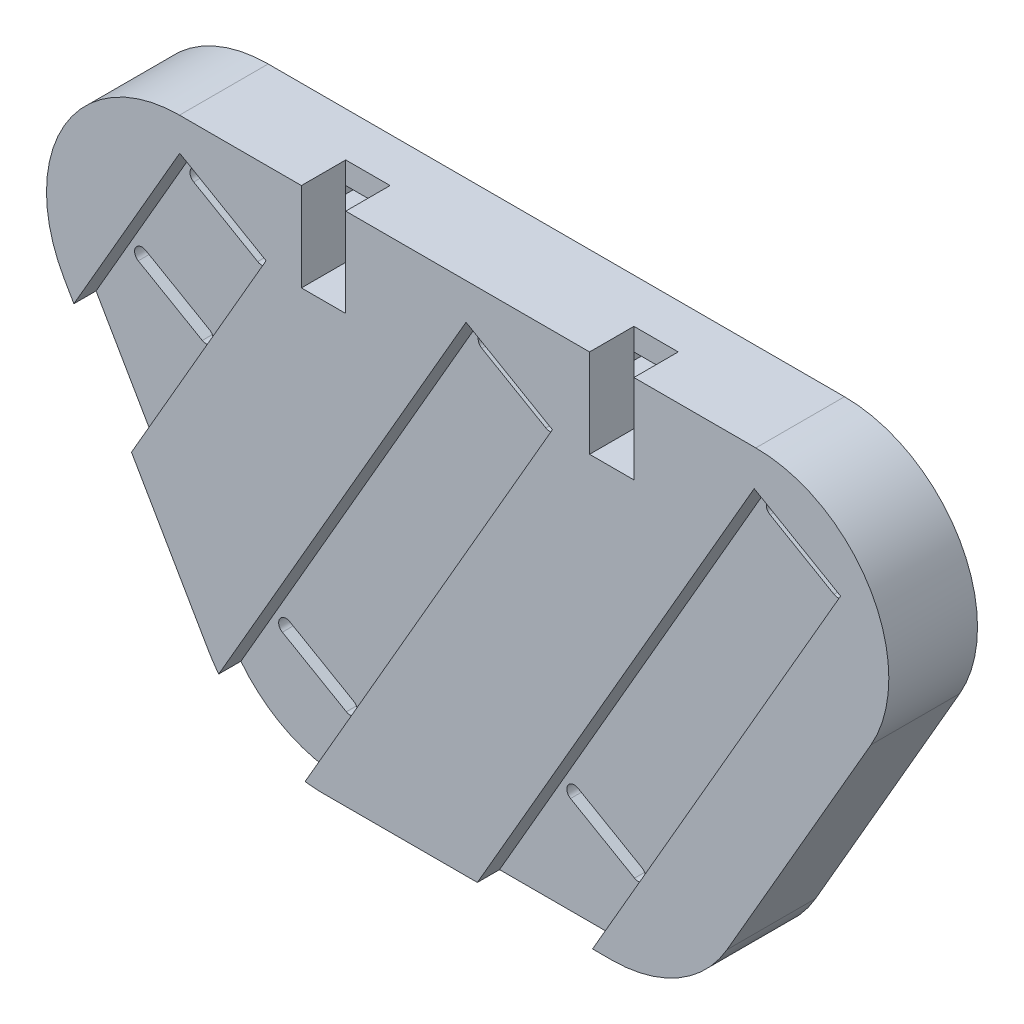
SolidWorks part; units mm, degrees
ref_plane "Front Plane" through (0, 0, 0) normal (0, 0, 1) x (1, 0, 0)
ref_plane "Top Plane" through (0, 0, 0) normal (0, 1, 0) x (1, 0, 0)
ref_plane "Right Plane" through (0, 0, 0) normal (1, 0, 0) x (0, 0, -1)
sketch "Sketch1" plane through (0, 0, 0) normal (0, 0, 1) x (1, 0, 0)
  line L0 (0, 0) -> (-19.5, 0) construction
  line L1 (-9.75, -16.8875) -> (-29.25, -16.8875) construction
  line L2 (0, 0) -> (-9.75, -16.8875) construction
  line L3 (-9.75, -16.8875) -> (-19.5, 0) construction
  line L4 (-19.5, 0) -> (-29.25, -16.8875) construction
  line L5 (-29.25, -16.8875) -> (-39, 0) construction
  line L6 (-39, 0) -> (-19.5, 0) construction
  line L7 (8.9827, 0.5584) -> (-5.4199, -24.3875) construction
  line L8 (-5.4199, -24.3875) -> (-33.5801, -24.3875) construction
  line L9 (-33.5801, -24.3875) -> (-47.9827, 0.5584) construction
  line L10 (-43.9749, 7.5) -> (4.9749, 7.5) construction
  line L11 (7.7942, -4.5) -> (-1.9558, -21.3875)
  line L12 (-9.75, -25.8875) -> (-29.25, -25.8875)
  line L13 (-37.0442, -21.3875) -> (-46.7942, -4.5)
  line L14 (-39, 9) -> (0, 9)
  line L15 (1.7814, -11.9145) -> (3.0804, -12.6645) construction
  line L16 (-19.5, -24.3875) -> (-19.5, -25.8875) construction
  line L17 (-40.7814, -11.9145) -> (-42.0804, -12.6645) construction
  line L18 (-19.5, 7.5) -> (-19.5, 9) construction
  circle A0 centre (-29.25, -16.8875) radius 7.5
  circle A1 centre (-19.5, 0) radius 7.5
  circle A2 centre (0, 0) radius 7.5
  circle A3 centre (0, 0) radius 7.5
  circle A4 centre (-9.75, -16.8875) radius 7.5
  circle A5 centre (-39, 0) radius 7.5
  arc A6 (7.7942, -4.5) -> (0, 9) centre (0, 0) ccw
  arc A7 (-39, 9) -> (-46.7942, -4.5) centre (-39, 0) ccw
  arc A8 (-1.9558, -21.3875) -> (-9.75, -25.8875) centre (-9.75, -16.8875) cw
  arc A9 (-29.25, -25.8875) -> (-37.0442, -21.3875) centre (-29.25, -16.8875) cw
  point P28 (1.7814, -11.9145)
  point P30 (-19.5, -24.3875)
  point P32 (-40.7814, -11.9145)
  point P35 (-19.5, 9)
  dimension "D2" = 15
  dimension "D3" = 19.5
  dimension "D4" = 1.5
  dimension "D5" = 1.5
  dimension "D1" = 0.25
extrude "Boss-Extrude1" add sketch "Sketch1" along normal blind 3
sketch "Sketch2" plane through (0, 0, 3) normal (0, 0, 1) x (1, 0, 0)
  line L0 (-1.9558, -21.3875) -> (7.7942, -4.5) construction
  line L1 (0, 9) -> (-39, 9) construction
  line L2 (-46.7942, -4.5) -> (-37.0442, -21.3875) construction
  line L3 (-29.25, -25.8875) -> (-9.75, -25.8875) construction
  line L4 (-1.9558, -21.3875) -> (7.7942, -4.5)
  line L5 (0, 9) -> (-39, 9)
  line L6 (-46.7942, -4.5) -> (-37.0442, -21.3875)
  line L7 (-29.25, -25.8875) -> (-9.75, -25.8875)
  line L8 (4.0401, 1.9976) -> (-0.2901, 4.4976) construction
  line L9 (3.7901, 1.5646) -> (-0.5401, 4.0646)
  line L10 (4.2901, 2.4306) -> (-0.0401, 4.9306)
  line L11 (-9.4599, -21.3851) -> (-13.7901, -18.8851) construction
  line L12 (-9.7099, -21.8181) -> (-14.0401, -19.3181)
  line L13 (-9.2099, -20.9521) -> (-13.5401, -18.4521)
  line L14 (1.875, 3.2476) -> (-11.625, -20.1351) construction
  line L15 (-31.125, -20.1351) -> (-29.25, -16.8875) construction
  line L16 (0, 0) -> (1.875, 3.2476) construction
  line L17 (1.875, 3.2476) -> (3.75, 6.4952) construction
  line L18 (-11.625, -20.1351) -> (-13.5, -23.3827) construction
  line L19 (-11.625, -20.1351) -> (-9.75, -16.8875) construction
  line L20 (-17.625, 3.2476) -> (-15.75, 6.4952) construction
  line L21 (-17.625, 3.2476) -> (-31.125, -20.1351) construction
  line L22 (-19.5, 0) -> (-17.625, 3.2476) construction
  line L23 (-31.125, -20.1351) -> (-33, -23.3827) construction
  line L24 (-15.4599, 1.9976) -> (-19.7901, 4.4976) construction
  line L25 (-15.7099, 1.5646) -> (-20.0401, 4.0646)
  line L26 (-15.2099, 2.4306) -> (-19.5401, 4.9306)
  line L27 (-28.9599, -21.3851) -> (-33.2901, -18.8851) construction
  line L28 (-29.2099, -21.8181) -> (-33.5401, -19.3181)
  line L29 (-28.7099, -20.9521) -> (-33.0401, -18.4521)
  line L30 (-34.9599, 1.9976) -> (-39.2901, 4.4976) construction
  line L31 (-35.2099, 1.5646) -> (-39.5401, 4.0646)
  line L32 (-34.7099, 2.4306) -> (-39.0401, 4.9306)
  line L33 (-38.7099, -4.4976) -> (-43.0401, -1.9976) construction
  line L34 (-38.9599, -4.9306) -> (-43.2901, -2.4306)
  line L35 (-38.4599, -4.0646) -> (-42.7901, -1.5646)
  line L36 (-37.125, 3.2476) -> (-40.875, -3.2476) construction
  line L37 (-37.125, 3.2476) -> (-35.25, 6.4952) construction
  line L38 (-40.875, -3.2476) -> (-42.75, -6.4952) construction
  line L39 (-37.125, 3.2476) -> (-39, 0) construction
  arc A0 (-9.75, -25.8875) -> (-1.9558, -21.3875) centre (-9.75, -16.8875) ccw construction
  arc A1 (7.7942, -4.5) -> (0, 9) centre (0, 0) ccw construction
  arc A2 (-39, 9) -> (-46.7942, -4.5) centre (-39, 0) ccw construction
  arc A3 (-37.0442, -21.3875) -> (-29.25, -25.8875) centre (-29.25, -16.8875) ccw construction
  arc A4 (-9.75, -25.8875) -> (-1.9558, -21.3875) centre (-9.75, -16.8875) ccw
  arc A5 (7.7942, -4.5) -> (0, 9) centre (0, 0) ccw
  arc A6 (-39, 9) -> (-46.7942, -4.5) centre (-39, 0) ccw
  arc A7 (-37.0442, -21.3875) -> (-29.25, -25.8875) centre (-29.25, -16.8875) ccw
  circle A8 centre (-39, 0) radius 7.5 construction
  circle A9 centre (-29.25, -16.8875) radius 7.5 construction
  circle A10 centre (-19.5, 0) radius 7.5 construction
  circle A11 centre (-9.75, -16.8875) radius 7.5 construction
  circle A12 centre (0, 0) radius 7.5 construction
  circle A13 centre (-39, 0) radius 7.5
  circle A14 centre (-29.25, -16.8875) radius 7.5
  circle A15 centre (-19.5, 0) radius 7.5
  circle A16 centre (-9.75, -16.8875) radius 7.5
  circle A17 centre (0, 0) radius 7.5
  arc A18 (3.7901, 1.5646) -> (4.2901, 2.4306) centre (4.0401, 1.9976) ccw
  arc A19 (-0.0401, 4.9306) -> (-0.5401, 4.0646) centre (-0.2901, 4.4976) ccw
  arc A20 (-9.7099, -21.8181) -> (-9.2099, -20.9521) centre (-9.4599, -21.3851) ccw
  arc A21 (-13.5401, -18.4521) -> (-14.0401, -19.3181) centre (-13.7901, -18.8851) ccw
  arc A22 (-15.7099, 1.5646) -> (-15.2099, 2.4306) centre (-15.4599, 1.9976) ccw
  arc A23 (-19.5401, 4.9306) -> (-20.0401, 4.0646) centre (-19.7901, 4.4976) ccw
  arc A24 (-29.2099, -21.8181) -> (-28.7099, -20.9521) centre (-28.9599, -21.3851) ccw
  arc A25 (-33.0401, -18.4521) -> (-33.5401, -19.3181) centre (-33.2901, -18.8851) ccw
  arc A26 (-35.2099, 1.5646) -> (-34.7099, 2.4306) centre (-34.9599, 1.9976) ccw
  arc A27 (-39.0401, 4.9306) -> (-39.5401, 4.0646) centre (-39.2901, 4.4976) ccw
  arc A28 (-38.9599, -4.9306) -> (-38.4599, -4.0646) centre (-38.7099, -4.4976) ccw
  arc A29 (-42.7901, -1.5646) -> (-43.2901, -2.4306) centre (-43.0401, -1.9976) ccw
  point P8 (-37.125, 3.2476)
  point P25 (1.875, 3.2476)
  point P32 (-11.625, -20.1351)
  point P45 (-17.625, 3.2476)
  point P52 (-31.125, -20.1351)
  point P64 (-40.875, -3.2476)
  circle M1 centre (-9.75, -16.8875) radius 7.5
  circle M2 centre (0, 0) radius 7.5
  arc M3 (7.7942, -4.5) -> (0, 9) centre (0, 0) ccw
  line M4 (0, 9) -> (-39, 9)
  arc M5 (-39, 9) -> (-46.7942, -4.5) centre (-39, 0) ccw
  line M6 (-46.7942, -4.5) -> (-37.0442, -21.3875)
  arc M7 (-37.0442, -21.3875) -> (-29.25, -25.8875) centre (-29.25, -16.8875) ccw
  line M8 (-29.25, -25.8875) -> (-9.75, -25.8875)
  arc M9 (-9.75, -25.8875) -> (-1.9558, -21.3875) centre (-9.75, -16.8875) ccw
  line M10 (-1.9558, -21.3875) -> (7.7942, -4.5)
  circle M11 centre (-19.5, 0) radius 7.5
  circle M12 centre (-29.25, -16.8875) radius 7.5
  circle M13 centre (-39, 0) radius 7.5
  dimension "D1" = 1
  dimension "D2" = 5
extrude "Boss-Extrude2" add sketch "Sketch2" along normal blind 1.5 contours A21 L13 A20 L12 M1 | M10 M3 M4 M5 M6 M7 M8 M9 M2 M11 M13 M12 M1 | A19 L10 A18 L9 M2 | A23 L26 A22 L25 M11 | A25 L29 A24 L28 M12 | A29 L35 A28 L34 A27 L32 A26 L31 M13 region at (-5.5841, -24.103, 3) region at (-39, 0, 3) region at (-29.1865, -16.7776, 3) region at (-19.5635, -0.1099, 3) region at (-9.6865, -16.7776, 3) region at (-0.0635, -0.1099, 3)
sketch "Sketch3" plane through (0, 0, 4.5) normal (0, 0, 1) x (1, 0, 0)
  line L0 (-46.7942, -4.5) -> (-37.0442, -21.3875) construction
  line L1 (-29.25, -25.8875) -> (-9.75, -25.8875) construction
  line L2 (-1.9558, -21.3875) -> (7.7942, -4.5) construction
  line L3 (0, 9) -> (-39, 9) construction
  line L4 (-46.7942, -4.5) -> (-37.0442, -21.3875)
  line L5 (-29.25, -25.8875) -> (-9.75, -25.8875)
  line L6 (-1.9558, -21.3875) -> (7.7942, -4.5)
  line L7 (0, 9) -> (-39, 9)
  line L8 (5.7353, 3.1839) -> (-9.6397, -23.4464)
  line L9 (5.7353, 3.1839) -> (-0.1103, 6.5589)
  line L10 (-9.6397, -23.4464) -> (-15.4853, -20.0714)
  line L11 (-0.1103, 6.5589) -> (-15.4853, -20.0714)
  line L12 (5.7353, 3.1839) -> (-15.4853, -20.0714) construction
  line L13 (-9.6397, -23.4464) -> (-0.1103, 6.5589) construction
  line L14 (-11.625, -20.1351) -> (-13.5, -23.3827) construction
  line L15 (-11.625, -20.1351) -> (-13.5, -23.3827) construction
  line L16 (-11.875, -20.5681) -> (-12.5625, -21.7589) construction
  line L17 (-9.7099, -21.8181) -> (-14.0401, -19.3181) construction
  line L18 (-14.2231, -18.6351) -> (-14.5478, -18.4476) construction
  line L19 (1.875, 3.2476) -> (-11.625, -20.1351) construction
  line L20 (1.875, 3.2476) -> (-11.625, -20.1351) construction
  line L21 (-31.125, -20.1351) -> (-33, -23.3827) construction
  line L22 (-17.625, 3.2476) -> (-31.125, -20.1351) construction
  line L23 (-31.125, -20.1351) -> (-33, -23.3827) construction
  line L24 (-17.625, 3.2476) -> (-31.125, -20.1351) construction
  line L25 (-13.7647, 3.1839) -> (-29.1397, -23.4464)
  line L26 (-13.7647, 3.1839) -> (-19.6103, 6.5589)
  line L27 (-29.1397, -23.4464) -> (-34.9853, -20.0714)
  line L28 (-19.6103, 6.5589) -> (-34.9853, -20.0714)
  line L29 (-13.7647, 3.1839) -> (-34.9853, -20.0714) construction
  line L30 (-29.1397, -23.4464) -> (-19.6103, 6.5589) construction
  line L31 (-32.8571, -19.1351) -> (-34.0478, -18.4476) construction
  line L32 (-31.375, -20.5681) -> (-32.0625, -21.7589) construction
  line L33 (-29.2099, -21.8181) -> (-33.5401, -19.3181) construction
  line L34 (-33.1397, 3.4004) -> (-42.2476, -12.375)
  line L35 (-33.1397, 3.4004) -> (-38.9853, 6.7754)
  line L36 (-9.6397, -23.4464) -> (-15.4853, -20.0714)
  line L37 (-38.9853, 6.7754) -> (-46.1447, -5.625)
  line L38 (-33.1397, 3.4004) -> (-45.4579, -6.8146) construction
  line L39 (-42.2476, -12.375) -> (-38.9853, 6.7754) construction
  line L40 (-37.125, 3.2476) -> (-40.875, -3.2476) construction
  line L41 (-36.875, 3.6806) -> (-36.0625, 5.0879) construction
  line L42 (-34.7099, 2.4306) -> (-39.0401, 4.9306) construction
  line L43 (-36.0625, 5.0879) -> (-35.25, 6.4952) construction
  line L44 (-9.6397, -23.4464) -> (-11.049, -25.8875)
  line L45 (-15.4853, -20.0714) -> (-18.8433, -25.8875)
  line L47 (-29.1397, -23.4464) -> (-34.9853, -20.0714)
  line L48 (-29.1397, -23.4464) -> (-30.4988, -25.8004)
  line L49 (-34.9853, -20.0714) -> (-36.3444, -22.4254)
  arc A0 (-37.0442, -21.3875) -> (-29.25, -25.8875) centre (-29.25, -16.8875) ccw construction
  arc A1 (-9.75, -25.8875) -> (-1.9558, -21.3875) centre (-9.75, -16.8875) ccw construction
  arc A2 (7.7942, -4.5) -> (0, 9) centre (0, 0) ccw construction
  arc A3 (-39, 9) -> (-46.7942, -4.5) centre (-39, 0) ccw construction
  arc A4 (-37.0442, -21.3875) -> (-29.25, -25.8875) centre (-29.25, -16.8875) ccw
  arc A5 (-9.75, -25.8875) -> (-1.9558, -21.3875) centre (-9.75, -16.8875) ccw
  arc A6 (7.7942, -4.5) -> (0, 9) centre (0, 0) ccw
  arc A7 (-39, 9) -> (-46.7942, -4.5) centre (-39, 0) ccw
  arc A8 (-13.5401, -18.4521) -> (-14.0401, -19.3181) centre (-13.7901, -18.8851) ccw construction
  arc A9 (-33.0401, -18.4521) -> (-33.5401, -19.3181) centre (-33.2901, -18.8851) ccw construction
  point P13 (-4.875, -8.4437)
  point P30 (-12.5625, -21.7589)
  point P33 (-4.875, -8.4437)
  point P35 (-24.375, -8.4437)
  point P49 (-24.375, -8.4437)
  point P50 (-40.6165, -2.7998)
  line M15 (-1.9558, -21.3875) -> (7.7942, -4.5)
  arc M16 (7.7942, -4.5) -> (0, 9) centre (0, 0) ccw
  line M17 (0, 9) -> (-39, 9)
  arc M18 (-39, 9) -> (-46.7942, -4.5) centre (-39, 0) ccw
  line M19 (-46.7942, -4.5) -> (-37.0442, -21.3875)
  arc M20 (-37.0442, -21.3875) -> (-29.25, -25.8875) centre (-29.25, -16.8875) ccw
  line M21 (-29.25, -25.8875) -> (-9.75, -25.8875)
  arc M22 (-9.75, -25.8875) -> (-1.9558, -21.3875) centre (-9.75, -16.8875) ccw
extrude "Boss-Extrude3" add sketch "Sketch3" along normal blind 1.5 contours L37 L35 L34 L4 L28 L26 L25 L27 L11 L9 L8 L10 M20 M21 M22 M15 M16 M17 M18 M19 region at (-46.2155, 4.1659, 4.5)
sketch "Sketch9" plane through (0, 0, 6) normal (0, 0, 1) x (1, 0, 0)
  line L0 (-39, 9) -> (-19.5, 9)
  line L1 (0, 9) -> (-39, 9) construction
  line L2 (-19.5, 9) -> (0, 9) construction
  line L3 (-29.25, 9) -> (-29.25, 3) construction
  line L4 (-27.75, 3) -> (-30.75, 3)
  line L5 (-27.75, 3) -> (-27.75, 9)
  line L6 (-27.75, 9) -> (-30.75, 9)
  line L7 (-30.75, 3) -> (-30.75, 9)
  line L8 (-27.75, 3) -> (-30.75, 9) construction
  line L9 (-27.75, 9) -> (-30.75, 3) construction
  line L10 (-8.25, 3) -> (-11.25, 3)
  line L11 (-8.25, 3) -> (-8.25, 9)
  line L12 (-8.25, 9) -> (-11.25, 9)
  line L13 (-11.25, 3) -> (-11.25, 9)
  line L14 (-8.25, 3) -> (-11.25, 9) construction
  line L15 (-8.25, 9) -> (-11.25, 3) construction
  line L16 (-9.75, 9) -> (-9.75, 3) construction
  point P5 (-29.25, 6)
  point P12 (-9.75, 6)
  dimension "D1" = 3
  dimension "D2" = 6
extrude "Cut-Extrude4" cut sketch "Sketch9" against normal blind 3 contours L10 L13 L12 L11 | L4 L7 L6 L5
sketch "Sketch4" plane through (0, 0, 0) normal (0, 0, -1) x (-1, 0, 0)
  line L0 (29.25, -25.8875) -> (9.75, -25.8875) construction
  line L1 (22, -25.8875) -> (17, -25.8875)
  line L2 (22, -25.8875) -> (22, -22.8875)
  line L3 (22, -22.8875) -> (17, -22.8875)
  line L4 (17, -25.8875) -> (17, -22.8875)
  line L5 (22, -25.8875) -> (17, -22.8875) construction
  line L6 (22, -22.8875) -> (17, -25.8875) construction
  line L7 (29.25, -25.8875) -> (9.75, -25.8875)
  line L8 (0, 9) -> (39, 9) construction
  line L9 (46.7942, -4.5) -> (37.0442, -21.3875) construction
  line L10 (1.9558, -21.3875) -> (-7.7942, -4.5) construction
  line L11 (0, 9) -> (39, 9)
  line L12 (46.7942, -4.5) -> (37.0442, -21.3875)
  line L13 (1.9558, -21.3875) -> (-7.7942, -4.5)
  line L14 (40.5712, -9.2787) -> (43.1692, -10.7787)
  line L15 (40.5712, -9.2787) -> (38.0712, -13.6088)
  line L16 (43.1692, -10.7787) -> (40.6692, -15.1088)
  line L17 (38.0712, -13.6088) -> (40.6692, -15.1088)
  line L18 (40.5712, -9.2787) -> (40.6692, -15.1088) construction
  line L19 (43.1692, -10.7787) -> (38.0712, -13.6088) construction
  line L20 (-1.5712, -9.2787) -> (-4.1692, -10.7787)
  line L21 (-1.5712, -9.2787) -> (0.9288, -13.6088)
  line L22 (-4.1692, -10.7787) -> (-1.6692, -15.1088)
  line L23 (0.9288, -13.6088) -> (-1.6692, -15.1088)
  line L24 (-1.5712, -9.2787) -> (-1.6692, -15.1088) construction
  line L25 (-4.1692, -10.7787) -> (0.9288, -13.6088) construction
  line L26 (41.9192, -12.9437) -> (3.9115, 9) construction
  line L27 (12.25, 6) -> (7.25, 6)
  line L28 (12.25, 6) -> (12.25, 9)
  line L29 (12.25, 9) -> (7.25, 9)
  line L30 (7.25, 6) -> (7.25, 9)
  line L31 (12.25, 6) -> (7.25, 9) construction
  line L32 (12.25, 9) -> (7.25, 6) construction
  line L33 (31.75, 6) -> (26.75, 6)
  line L34 (31.75, 6) -> (31.75, 9)
  line L35 (31.75, 9) -> (26.75, 9)
  line L36 (26.75, 6) -> (26.75, 9)
  line L37 (31.75, 6) -> (26.75, 9) construction
  line L38 (31.75, 9) -> (26.75, 6) construction
  line L39 (-2.9192, -12.9437) -> (35.0885, 9) construction
  line L40 (22, -24.3875) -> (17, -24.3875)
  line L41 (-0.3702, -14.3588) -> (-2.8702, -10.0287)
  line L42 (12.25, 7.5) -> (7.25, 7.5)
  line L43 (39.3702, -14.3588) -> (41.8702, -10.0287)
  line L44 (26.75, 7.5) -> (31.75, 7.5)
  point P0 (19.5, -24.3875)
  point P5 (9.75, 7.5)
  point P8 (19.5, -25.8875)
  point P15 (40.6202, -12.1937)
  point P16 (-1.6202, -12.1937)
  point P29 (29.25, 7.5)
  dimension "D1" = 5
  dimension "D2" = 3
extrude "Cut-Extrude5" cut sketch "Sketch4" against normal blind 3 contours L41 L23 L21 L20 | L28 L42 L30 L27 | L44 L36 L33 L34 | L17 L43 L14 L15 | L40 L2 L3 L4 region at (-19.5, -23.6375, 0) region at (-9.75, 6.75, 0) region at (-29.25, 6.75, 0) region at (-39.9707, -11.8187, 0) region at (0.9707, -11.8187, 0)
equation "\"D3@Sketch1\"=\"D2@Sketch1\"+4.5"
equation "\"D1@Sketch2\"=.65+.35"
